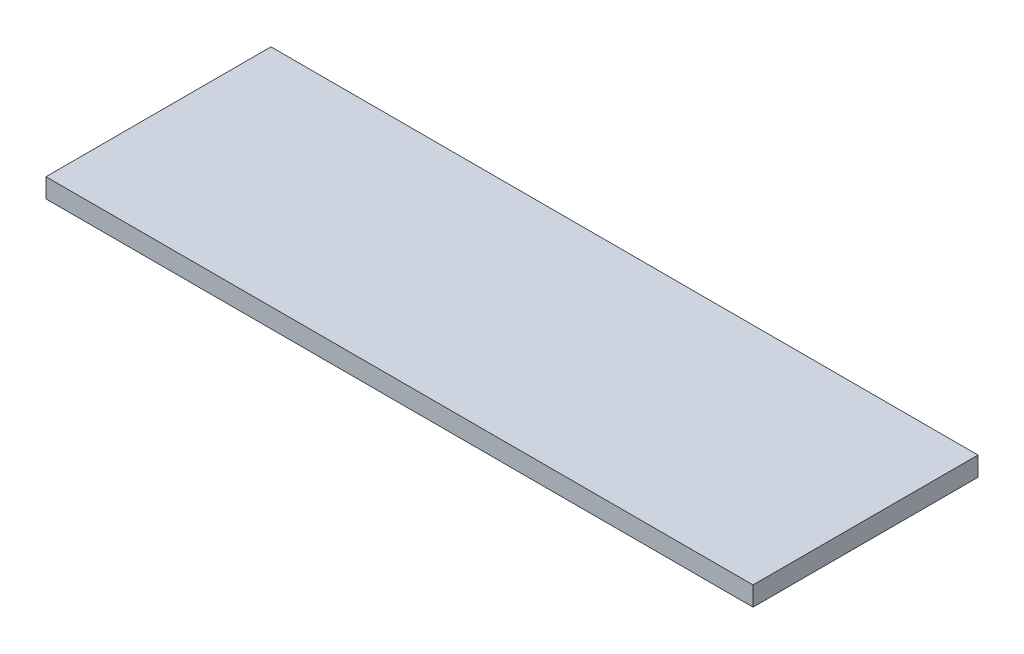
SolidWorks part; units mm, degrees
material "Acrylic (Medium-high impact)"
ref_plane "Front Plane" through (0, 0, 0) normal (0, 0, 1) x (1, 0, 0)
ref_plane "Top Plane" through (0, 0, 0) normal (0, 1, 0) x (1, 0, 0)
ref_plane "Right Plane" through (0, 0, 0) normal (1, 0, 0) x (0, 0, -1)
sketch "Sketch1" plane through (0, 0, 0) normal (0, 1, 0) x (1, 0, 0)
  line L1 (-361.9051, 70) -> (-141.9051, 70)
  line L2 (-361.9051, 70) -> (-361.9051, 0)
  line L3 (-361.9051, 0) -> (-141.9051, 0)
  line L4 (-141.9051, 70) -> (-141.9051, 0)
  dimension "D1" = 70
  dimension "D2" = 220
extrude "Boss-Extrude1" add sketch "Sketch1" along normal blind 6
